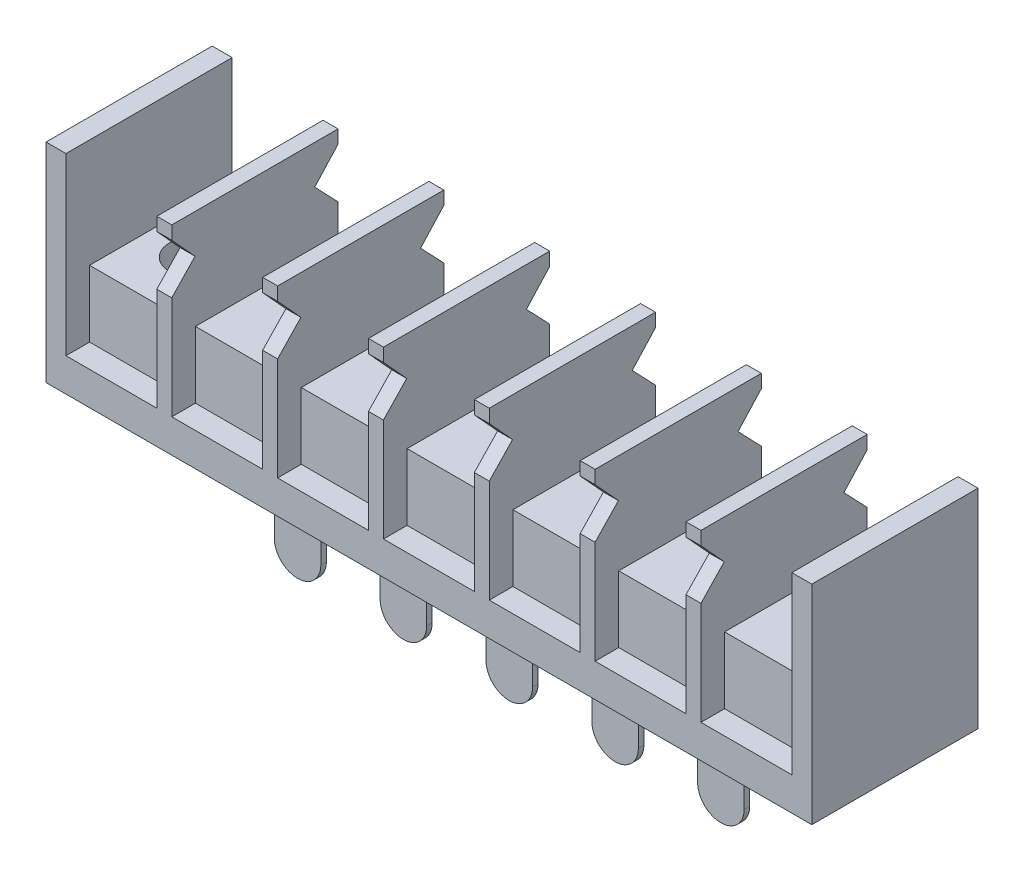
SolidWorks part; units mm, degrees
ref_plane "前视基准面" through (0, 0, 0) normal (0, 0, 1) x (1, 0, 0)
ref_plane "上视基准面" through (0, 0, 0) normal (0, 1, 0) x (1, 0, 0)
ref_plane "右视基准面" through (0, 0, 0) normal (1, 0, 0) x (0, 0, -1)
sketch "草图1" plane through (0, 0, 0) normal (0, 1, 0) x (1, 0, 0)
  line L0 (0, 12.7565) -> (0, -11.1323) construction
  line L1 (-34.55, -7.5) -> (34.55, -7.5)
  line L2 (-34.55, -7.5) -> (-34.55, 7.5)
  line L3 (-34.55, 7.5) -> (34.55, 7.5)
  line L4 (34.55, -7.5) -> (34.55, 7.5)
  line L5 (-29.1602, 0) -> (32.7116, 0) construction
  dimension "D1" = 69.1
  dimension "D2" = 15
extrude "拉伸1" add sketch "草图1" along normal blind 18.8
sketch "草图2" plane through (0, 18.8, 0) normal (0, 1, 0) x (-1, 0, 0)
  line L0 (-34.55, -7.5) -> (34.55, -7.5) construction
  line L1 (-32.75, -7.5) -> (32.75, -7.5)
  line L2 (-32.75, -7.5) -> (-32.75, 7.5)
  line L3 (-32.75, 7.5) -> (32.75, 7.5)
  line L4 (32.75, -7.5) -> (32.75, 7.5)
  line L5 (34.55, 7.5) -> (-34.55, 7.5) construction
  line L6 (-34.55, 7.5) -> (-34.55, -7.5) construction
  line L7 (34.55, -7.5) -> (34.55, 7.5) construction
  dimension "D1" = 1.8
  dimension "D2" = 1.8
extrude "切除-拉伸1" cut sketch "草图2" against normal offset from surface (0.8 mm away) 18 up to face at (0, 0, 0)
sketch "草图4" plane through (0, 18, 0) normal (0, 1, 0) x (-1, 0, 0)
  line L0 (32.75, 7.5) -> (-32.75, 7.5) construction
  line L1 (-32.75, -7.5) -> (-24.55, -7.5)
  line L2 (-32.75, -7.5) -> (-32.75, 7.5)
  line L3 (-32.75, 7.5) -> (-24.55, 7.5)
  line L4 (-24.55, -7.5) -> (-24.55, 7.5)
  line L5 (-23.2, -7.5) -> (-15, -7.5)
  line L6 (-23.2, -7.5) -> (-23.2, 7.5)
  line L7 (-23.2, 7.5) -> (-15, 7.5)
  line L8 (-15, -7.5) -> (-15, 7.5)
  line L9 (-13.65, -7.5) -> (-5.45, -7.5)
  line L10 (-13.65, -7.5) -> (-13.65, 7.5)
  line L11 (-13.65, 7.5) -> (-5.45, 7.5)
  line L12 (-5.45, -7.5) -> (-5.45, 7.5)
  line L13 (-4.1, -7.5) -> (4.1, -7.5)
  line L14 (-4.1, -7.5) -> (-4.1, 7.5)
  line L15 (-4.1, 7.5) -> (4.1, 7.5)
  line L16 (4.1, -7.5) -> (4.1, 7.5)
  line L17 (5.45, -7.5) -> (13.65, -7.5)
  line L18 (5.45, -7.5) -> (5.45, 7.5)
  line L19 (5.45, 7.5) -> (13.65, 7.5)
  line L20 (13.65, -7.5) -> (13.65, 7.5)
  line L21 (15, -7.5) -> (23.2, -7.5)
  line L22 (15, -7.5) -> (15, 7.5)
  line L23 (15, 7.5) -> (23.2, 7.5)
  line L24 (23.2, -7.5) -> (23.2, 7.5)
  line L25 (24.55, -7.5) -> (32.75, -7.5)
  line L26 (24.55, -7.5) -> (24.55, 7.5)
  line L27 (24.55, 7.5) -> (32.75, 7.5)
  line L28 (32.75, -7.5) -> (32.75, 7.5)
  dimension "D1" = 8.2
extrude "切除-拉伸2" cut sketch "草图4" against normal offset from surface (9 mm away) 9 up to face at (0, 0, 0)
sketch "草图5" plane through (0, 18, 0) normal (0, 1, 0) x (-1, 0, 0)
  line L1 (-32.75, 7.5) -> (-32.75, -7.5) construction
  line L2 (-32.75, -5.3676) -> (-24.55, -5.3676)
  line L3 (-32.75, -5.3676) -> (-32.75, -7.5)
  line L4 (-32.75, -7.5) -> (-24.55, -7.5)
  line L5 (29.9336, 0) -> (-26.6321, 0) construction
  line L6 (-24.55, -5.3676) -> (-24.55, -7.5)
  line L7 (-24.55, 5.3676) -> (-24.55, 7.5)
  line L8 (-32.75, 7.5) -> (-24.55, 7.5)
  line L9 (-32.75, 5.3676) -> (-32.75, 7.5)
  line L10 (-32.75, 5.3676) -> (-24.55, 5.3676)
  line L11 (-23.2, -5.3676) -> (-15, -5.3676)
  line L12 (-23.2, -5.3676) -> (-23.2, -7.5)
  line L13 (-23.2, -7.5) -> (-15, -7.5)
  line L14 (-15, -5.3676) -> (-15, -7.5)
  line L15 (-15, 5.3676) -> (-15, 7.5)
  line L16 (-23.2, 7.5) -> (-15, 7.5)
  line L17 (-23.2, 5.3676) -> (-23.2, 7.5)
  line L18 (-23.2, 5.3676) -> (-15, 5.3676)
  line L19 (-13.65, -5.3676) -> (-5.45, -5.3676)
  line L20 (-13.65, -5.3676) -> (-13.65, -7.5)
  line L21 (-13.65, -7.5) -> (-5.45, -7.5)
  line L22 (-5.45, -5.3676) -> (-5.45, -7.5)
  line L23 (-5.45, 5.3676) -> (-5.45, 7.5)
  line L24 (-13.65, 7.5) -> (-5.45, 7.5)
  line L25 (-13.65, 5.3676) -> (-13.65, 7.5)
  line L26 (-13.65, 5.3676) -> (-5.45, 5.3676)
  line L27 (-4.1, -5.3676) -> (4.1, -5.3676)
  line L28 (-4.1, -5.3676) -> (-4.1, -7.5)
  line L29 (-4.1, -7.5) -> (4.1, -7.5)
  line L30 (4.1, -5.3676) -> (4.1, -7.5)
  line L31 (4.1, 5.3676) -> (4.1, 7.5)
  line L32 (-4.1, 7.5) -> (4.1, 7.5)
  line L33 (-4.1, 5.3676) -> (-4.1, 7.5)
  line L34 (-4.1, 5.3676) -> (4.1, 5.3676)
  line L35 (5.45, -5.3676) -> (13.65, -5.3676)
  line L36 (5.45, -5.3676) -> (5.45, -7.5)
  line L37 (5.45, -7.5) -> (13.65, -7.5)
  line L38 (13.65, -5.3676) -> (13.65, -7.5)
  line L39 (13.65, 5.3676) -> (13.65, 7.5)
  line L40 (5.45, 7.5) -> (13.65, 7.5)
  line L41 (5.45, 5.3676) -> (5.45, 7.5)
  line L42 (5.45, 5.3676) -> (13.65, 5.3676)
  line L43 (15, -5.3676) -> (23.2, -5.3676)
  line L44 (15, -5.3676) -> (15, -7.5)
  line L45 (15, -7.5) -> (23.2, -7.5)
  line L46 (23.2, -5.3676) -> (23.2, -7.5)
  line L47 (23.2, 5.3676) -> (23.2, 7.5)
  line L48 (15, 7.5) -> (23.2, 7.5)
  line L49 (15, 5.3676) -> (15, 7.5)
  line L50 (15, 5.3676) -> (23.2, 5.3676)
  line L51 (24.55, -5.3676) -> (32.75, -5.3676)
  line L52 (24.55, -5.3676) -> (24.55, -7.5)
  line L53 (24.55, -7.5) -> (32.75, -7.5)
  line L54 (32.75, -5.3676) -> (32.75, -7.5)
  line L55 (32.75, 5.3676) -> (32.75, 7.5)
  line L56 (24.55, 7.5) -> (32.75, 7.5)
  line L57 (24.55, 5.3676) -> (24.55, 7.5)
  line L58 (24.55, 5.3676) -> (32.75, 5.3676)
extrude "切除-拉伸3" cut sketch "草图5" against normal offset from surface (15 mm away) 3 up to face at (0, 0, 0)
sketch "草图6" plane through (0, 0, 0) normal (0, -1, 0) x (1, 0, 0)
  line L0 (0, 12.0415) -> (0, -12.1791) construction
  line L1 (-6.3388, 0) -> (5.5048, 0) construction
  line L2 (2.1, 0.25) -> (-2.1, 0.25)
  line L3 (2.1, 0.25) -> (2.1, -0.25)
  line L4 (2.1, -0.25) -> (-2.1, -0.25)
  line L5 (-2.1, 0.25) -> (-2.1, -0.25)
  line L6 (11.65, 0.25) -> (7.45, 0.25)
  line L7 (11.65, 0.25) -> (11.65, -0.25)
  line L8 (11.65, -0.25) -> (7.45, -0.25)
  line L9 (7.45, 0.25) -> (7.45, -0.25)
  line L10 (21.2, 0.25) -> (17, 0.25)
  line L11 (21.2, 0.25) -> (21.2, -0.25)
  line L12 (21.2, -0.25) -> (17, -0.25)
  line L13 (17, 0.25) -> (17, -0.25)
  line L14 (-7.45, 0.25) -> (-11.65, 0.25)
  line L15 (-7.45, 0.25) -> (-7.45, -0.25)
  line L16 (-7.45, -0.25) -> (-11.65, -0.25)
  line L17 (-11.65, 0.25) -> (-11.65, -0.25)
  line L18 (-17, 0.25) -> (-21.2, 0.25)
  line L19 (-17, 0.25) -> (-17, -0.25)
  line L20 (-17, -0.25) -> (-21.2, -0.25)
  line L21 (-21.2, 0.25) -> (-21.2, -0.25)
  dimension "D1" = 0.5
  dimension "D2" = 4.2
extrude "拉伸2" add sketch "草图6" along normal blind 11.2
sketch "草图7" plane through (0, 9, 0) normal (0, 1, 0) x (-1, 0, 0)
  line L0 (0, -11.8563) -> (0, 13.0369) construction
  line L1 (-28.2468, 0) -> (30.271, 0) construction
  line L4 (-28.65, -9.8031) -> (-28.65, 12.0765) construction
  line L5 (-32.75, 5.3676) -> (-32.75, -5.3676) construction
  line L6 (-24.55, -5.3676) -> (-24.55, 5.3676) construction
  circle A0 centre (-28.65, 0) radius 2.25
  circle A1 centre (28.65, 0) radius 2.25
  dimension "D1" = 4.5
extrude "切除-拉伸4" cut sketch "草图7" against normal through all
sketch "草图8" plane through (24.55, 0, 0) normal (1, 0, 0) x (0, 0, -1)
  line L0 (7.5, 16.8) -> (5.4, 14.5)
  line L1 (5.4, 14.5) -> (7.5, 12.3)
  line L3 (7.5, 18) -> (-7.5, 18) construction
  line L4 (0, 21.7575) -> (0, -9.7526) construction
  line L6 (7.5, 18.8) -> (7.5, 0) construction
  line L8 (7.5, 16.8) -> (7.5, 12.3)
  line L9 (-7.5, 16.8) -> (-7.5, 12.3)
  line L10 (-5.4, 14.5) -> (-7.5, 12.3)
  line L11 (-7.5, 16.8) -> (-5.4, 14.5)
  dimension "D1" = 3.5
  dimension "D2" = 4.5
  dimension "D3" = 1.2
extrude "切除-拉伸5" cut sketch "草图8" against normal up to surface (57.3 mm away) up to face at (-32.75, 8.45, 0)
fillet "圆角1" radius 2.1 10 edges at (-21.2, -11.2, 0) (21.2, -11.2, 0) (17, -11.2, 0) (11.65, -11.2, 0) (7.45, -11.2, 0) (-2.1, -11.2, 0) (2.1, -11.2, 0) (-7.45, -11.2, 0) (-11.65, -11.2, 0) (-17, -11.2, 0)
